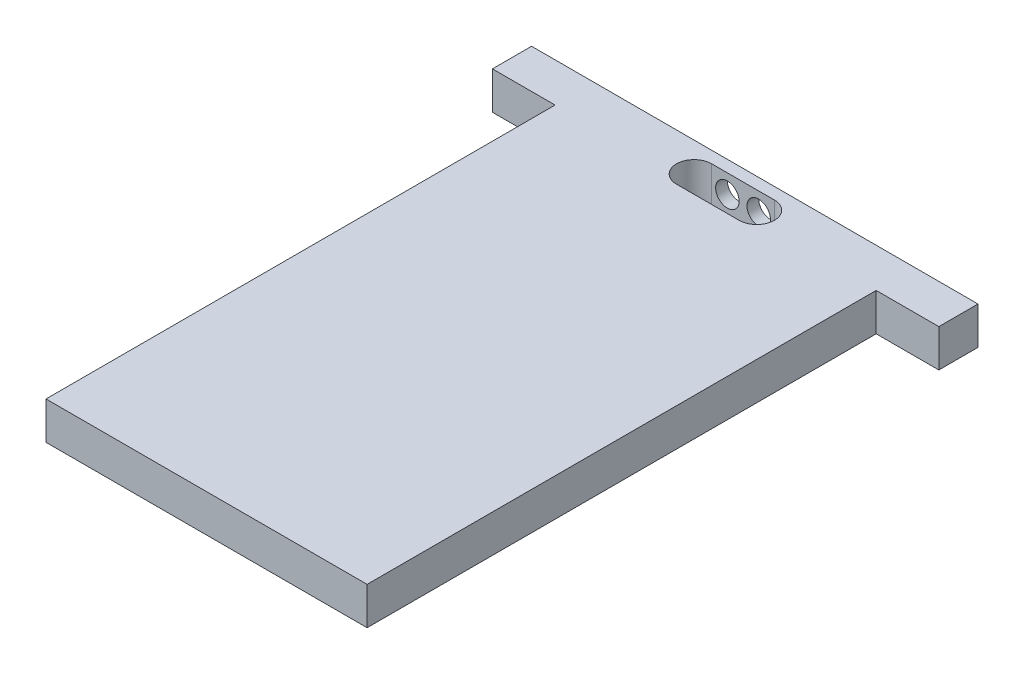
SolidWorks part; units mm, degrees
material "AISI 1020"
ref_plane "Front Plane" through (0, 0, 0) normal (0, 0, 1) x (1, 0, 0)
ref_plane "Top Plane" through (0, 0, 0) normal (0, 1, 0) x (1, 0, 0)
ref_plane "Right Plane" through (0, 0, 0) normal (1, 0, 0) x (0, 0, -1)
sketch "Sketch1" plane through (0, 0, 0) normal (0, 0, 1) x (1, 0, 0)
  line L1 (-20.5, -2.4) -> (20.5, -2.4)
  line L2 (-20.5, -2.4) -> (-20.5, 2.4)
  line L3 (-20.5, 2.4) -> (20.5, 2.4)
  line L4 (20.5, -2.4) -> (20.5, 2.4)
  line L5 (-20.5, -2.4) -> (20.5, 2.4) construction
  line L6 (-20.5, 2.4) -> (20.5, -2.4) construction
  point P0 (0, 0)
  dimension "D1" = 41
  dimension "D2" = 4.8
extrude "Boss-Extrude1" add sketch "Sketch1" along normal mid plane 65
sketch "Sketch2" plane through (0, 0, -32.5) normal (0, 0, 1) x (1, 0, 0)
  line L0 (20.5, -2.4) -> (20.5, 2.4) construction
  line L1 (-28.5, -2.4) -> (28.5, -2.4)
  line L2 (-28.5, -2.4) -> (-28.5, 2.4)
  line L3 (-28.5, 2.4) -> (28.5, 2.4)
  line L4 (28.5, -2.4) -> (28.5, 2.4)
  line L5 (-28.5, -2.4) -> (28.5, 2.4) construction
  line L6 (-28.5, 2.4) -> (28.5, -2.4) construction
  line L7 (0, 0) -> (0, -7.2336) construction
  dimension "D1" = 4.8
  dimension "D2" = 8
extrude "Boss-Extrude2" add sketch "Sketch2" against normal blind 5
sketch "Sketch3" plane through (0, 2.4, 0) normal (0, 1, 0) x (1, 0, 0)
  line L1 (28.5, 37.5) -> (-28.5, 37.5) construction
  line L2 (-4, 33.75) -> (4, 33.75) construction
  line L3 (-4, 36) -> (4, 36)
  line L4 (-4, 31.5) -> (4, 31.5)
  arc A1 (-4, 36) -> (-4, 31.5) centre (-4, 33.75) ccw
  arc A2 (4, 31.5) -> (4, 36) centre (4, 33.75) ccw
  circle A3 centre (0, 37.5) radius 2.5 construction
  point P0 (0, 33.75)
  point P1 (0, 33.75)
  point P4 (0, 37.5)
  dimension "D1" = 3.75
  dimension "D2" = 4.5
  dimension "D4" = 5
  dimension "D3" = 8
extrude "Cut-Extrude1" cut sketch "Sketch3" against normal through all
sketch "Sketch4" plane through (0, 0, -37.5) normal (0, 0, -1) x (-1, 0, 0)
  line L0 (0, 0) -> (0, 2.2954) construction
  circle A1 centre (2, 0) radius 1.5
  circle A2 centre (-2, 0) radius 1.5
  dimension "D1" = 3
  dimension "D2" = 2
extrude "Cut-Extrude2" cut sketch "Sketch4" against normal up to next
